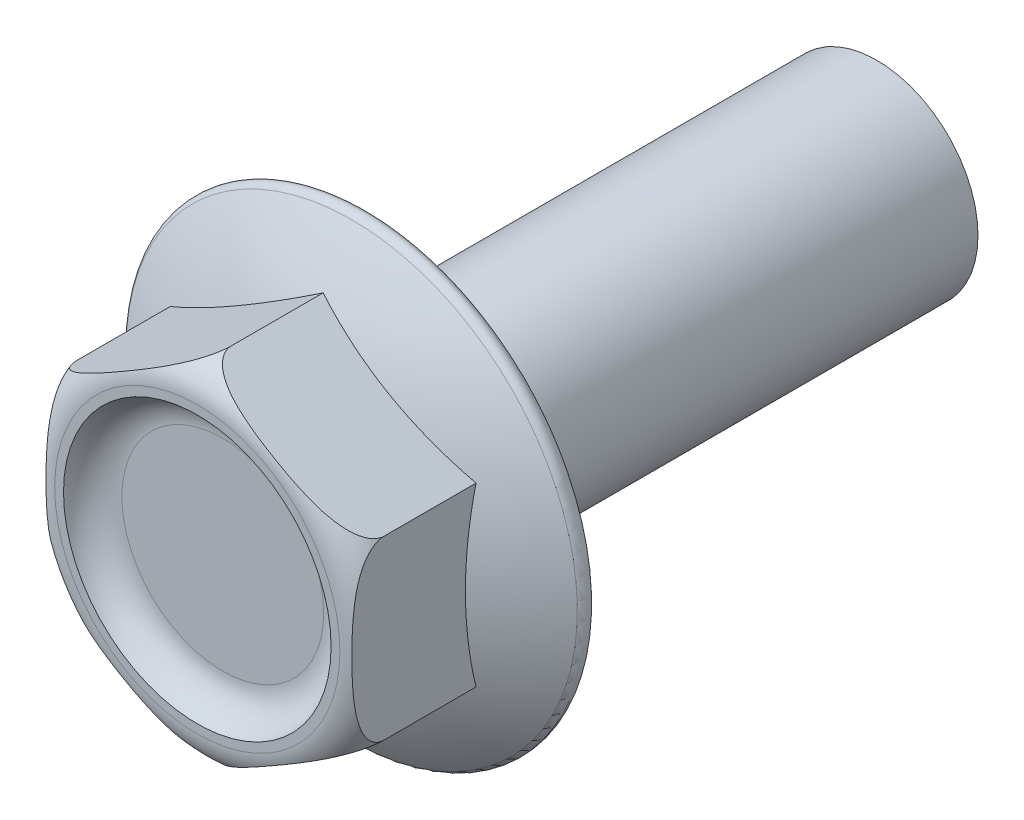
SolidWorks part; units mm, degrees
note: '?' marks a value the reader was unsure of.
extrude "Shank" add sketch "Shank Sketch" against normal blind 30
sketch "Shank Sketch" plane through (0, 0, 0) normal (0, 0, 1) x (1, 0, 0)
  line L0 (50, 0) -> (-50, 0) construction
  line L1 (0, -50) -> (0, 50) construction
  circle A0 centre (0, 0) radius 6
  dimension "Shank diameter" = 12
extrude "Head" add sketch "Head Sketch" along normal blind 10
sketch "Head Sketch" plane through (0, 0, 0) normal (0, 0, 1) x (1, 0, 0)
  line L0 (0, 10.3923) -> (9, 5.1962)
  line L1 (9, 5.1962) -> (9, -5.1962)
  line L2 (9, -5.1962) -> (0, -10.3923)
  line L3 (0, -10.3923) -> (-9, -5.1962)
  line L4 (-9, -5.1962) -> (-9, 5.1962)
  line L5 (-9, 5.1962) -> (0, 10.3923)
  line L6 (9, 5.1962) -> (-9, -5.1962) construction
  line L7 (0, 10.3923) -> (0, -10.3923) construction
  line L8 (-9, 5.1962) -> (9, -5.1962) construction
  point P0 (0, 0)
  dimension "D1" = 60
  dimension "D2" = 60
  dimension "Width across flats" = 18
ref_plane "Plane1" through (0, 0, 0) normal (0, 0, 1) x (1, 0, 0)
ref_plane "Plane2" through (0, 0, 0) normal (0, 1, 0) x (-1, 0, 0)
ref_plane "Plane3" through (0, 0, 0) normal (1, 0, 0) x (0, 0, -1)
other "Configuration Table"
sketch "Sketch3" plane through (0, 0, 0) normal (0, 1, 0) x (-1, 0, 0)
  line L0 (0, 0) -> (0, 10) construction
  line L1 (0, -30) -> (0, 0) construction
  line L4 (-13, 0) -> (0, 0)
  line L5 (0, 0) -> (0, 5)
  arc A0 (0, 5) -> (-13.2811, 0.9135) centre (0, -18.625) ccw
  arc A1 (-13, 0) -> (-13.2811, 0.9135) centre (-13, 0.5) cw
  dimension "D1" = 0.5
  dimension "D2" = 26
  dimension "D3" = 5
revolve "Flange" add sketch "Sketch3" angle 360 about L0
ref_axis "Axis1" through (0, 0, -80) along (0, 0, 1)?
sketch "Sketch5" plane through (0, 0, 0) normal (1, 0, 0) x (0, 0, -1)
  line L0 (-10, -8.3923) -> (-10, -10.3923)
  line L1 (-10, -10.3923) -> (-8, -10.3923)
  line L2 (-10, -10.3923) -> (-2.5915, -10.3923) construction
  line L3 (-10, -10.3923) -> (-10, -5.1962) construction
  line L5 (-15.0856, 0) -> (-8.1394, 0) construction
  line L6 (50, 0) -> (-50, 0) construction
  arc A0 (-10, -8.3923) -> (-8, -10.3923) centre (-8, -8.3923) ccw
  dimension "D1" = 2
revolve "Head Trim" cut sketch "Sketch5" angle 360 about L5
sketch "Sketch6" plane through (0, 0, 10) normal (0, 0, 1) x (1, 0, 0)
  circle A3 centre (0, 0) radius 7.875
  dimension "D1" = 15.75
extrude "Head Cut" cut sketch "Sketch6" against normal blind 1.5
fillet "Fillet1" radius 2 1 edges at (7.875, 0, 8.5)
fillet "Fillet2" radius 0.5 1 edges at (-6, 0, 0)
sketch "Thread End" plane through (0, 0, 0) normal (1, 0, 0) x (0, 0, -1)
  line L0 (0, 6) -> (0, 5.95)
  line L1 (30, 6) -> (0.5, 6) construction
  line L2 (0, 5.95) -> (30, 5.95)
  line L3 (30, 6) -> (0, 6)
  line L4 (21.5519, 0) -> (27.4271, 0) construction
  line L5 (30, 0) -> (0.5, 0) construction
  line L6 (30, -6) -> (30, 6) construction
  line L7 (30, 5.95) -> (30, 6)
  dimension "D1" = 0.05
  dimension "Length of thread" = 30
revolve "Thread Cut" cut sketch "Thread End" angle 360 about L4
cosmetic thread "Cosmetic Thread2" parameters "D2"=11
equation "\"D1@Sketch6\" = \"Width across flats@Head Sketch\"*7/8"
